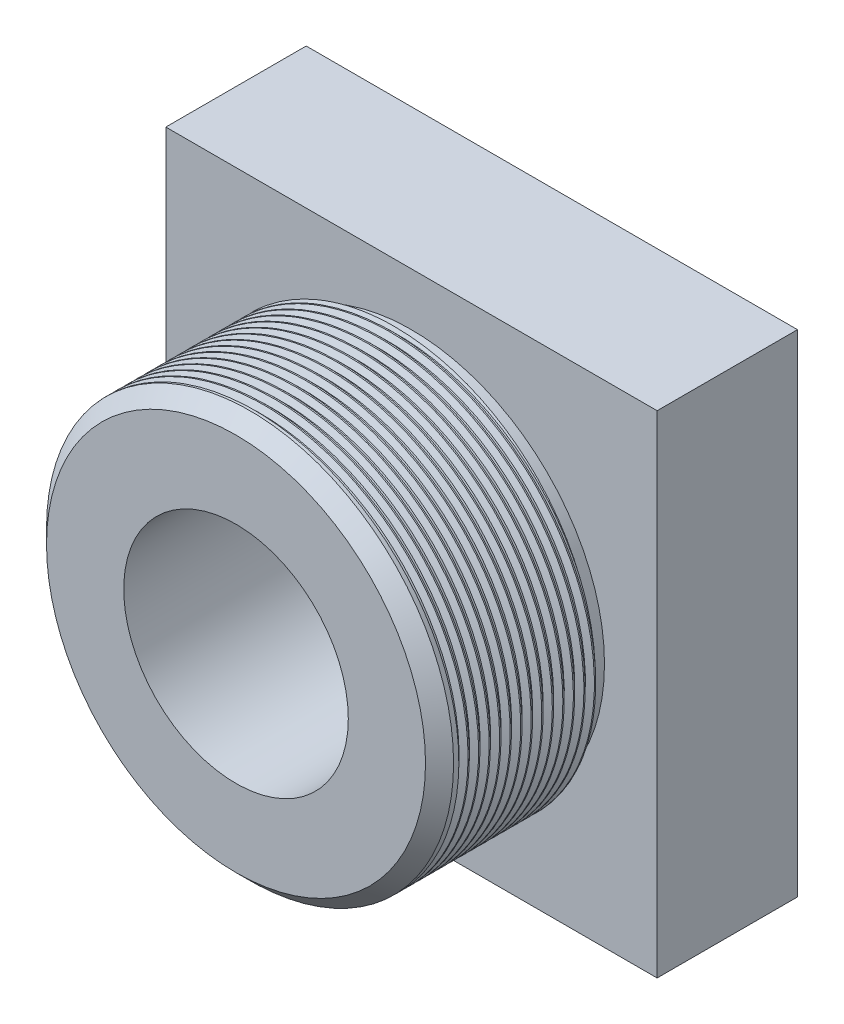
SolidWorks part; units mm, degrees
ref_plane "Front Plane" through (0, 0, 0) normal (0, 0, 1) x (1, 0, 0)
ref_plane "Top Plane" through (0, 0, 0) normal (0, 1, 0) x (1, 0, 0)
ref_plane "Right Plane" through (0, 0, 0) normal (1, 0, 0) x (0, 0, -1)
sketch "Sketch1" plane through (0, 0, 0) normal (0, 0, 1) x (1, 0, 0)
  line L1 (-35, -35) -> (35, -35)
  line L2 (-35, -35) -> (-35, 35)
  line L3 (-35, 35) -> (35, 35)
  line L4 (35, -35) -> (35, 35)
  line L5 (-35, -35) -> (35, 35) construction
  line L6 (-35, 35) -> (35, -35) construction
  circle A0 centre (0, 0) radius 16
  point P0 (0, 0)
  dimension "D3" = 32
  dimension "D1" = 70
  dimension "D2" = 70
extrude "Boss-Extrude1" add sketch "Sketch1" along normal blind 20
sketch "Sketch3" plane through (0, 0, 20) normal (0, 0, 1) x (1, 0, 0)
  circle A0 centre (0, 0) radius 27.5
  circle A1 centre (0, 0) radius 16 construction
  circle A2 centre (0, 0) radius 16
  dimension "D1" = 55
extrude "Boss-Extrude2" add sketch "Sketch3" along normal blind 2
sketch "Sketch4" plane through (0, 0, 22) normal (0, 0, 1) x (1, 0, 0)
  circle A2 centre (0, 0) radius 29
  circle A3 centre (0, 0) radius 16 construction
  circle A4 centre (0, 0) radius 16
  dimension "D1" = 58
extrude "Boss-Extrude3" add sketch "Sketch4" along normal blind 23
chamfer "Chamfer1" distance 2 angle 45 1 edges at (29, 0, 45)
thread "Thread1" pitch 1.5 method cut profile "Thread Profile1" start angle 0, offset 0, length 0, pitch 1.5, diameter 58
ref_plane "Plane1" through (-29, 0, 43) normal (0, -1, 0) x (-1, 0, 0)
sketch "Thread Profile1" plane through (-29, 0, 43) normal (0, -1, 0) x (-1, 0, 0)
  line L0 (0, 0) -> (0, 1.5) construction
  line L11 (0, 0) -> (0, 1.3125)
  line L12 (0, 1.3125) -> (-0.8119, 0.8437)
  line L13 (-0.8119, 0.8437) -> (-0.8119, 0.4687)
  line L15 (-0.8119, 0.4687) -> (0, 0)
  line L17 (-0.8119, 0.6562) -> (0, 0.6562) construction
  point P2 (0, 0)
  dimension "Pitch" = 1.5
  dimension "Profile_Angle" = 60
  dimension "Profile_Land" = 0.375
  dimension "Profile_Height" = 0.8119
